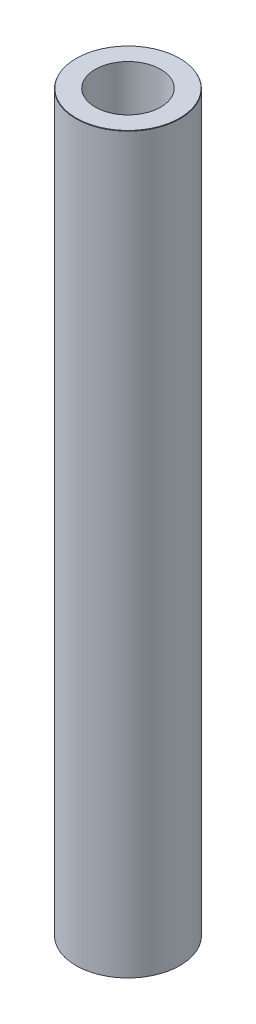
SolidWorks part; units mm, degrees
ref_plane "Front Plane" through (0, 0, 0) normal (0, 0, 1) x (1, 0, 0)
ref_plane "Top Plane" through (0, 0, 0) normal (0, 1, 0) x (1, 0, 0)
ref_plane "Right Plane" through (0, 0, 0) normal (1, 0, 0) x (0, 0, -1)
sketch "Sketch1" plane through (0, 0, 0) normal (0, 1, 0) x (1, 0, 0)
  circle A0 centre (0, 0) radius 42.5
  dimension "SHAFT_OD" = 85
extrude "Boss-Extrude1" add sketch "Sketch1" along normal blind 600
sketch "Sketch2" plane through (0, 0, 0) normal (0, 1, 0) x (1, 0, 0)
  circle A0 centre (0, 0) radius 26.7557
  dimension "BORE_D" = 53.5115
extrude "Cut-Extrude1" cut sketch "Sketch2" along normal through all
chamfer "Chamfer1" distance 0.368 angle 30 2 edges at (0, 600, 42.5) (0, 0, 42.5) first distance on face at (0, 600, 42.5) first distance on face at (0, 0, 26.7557)
